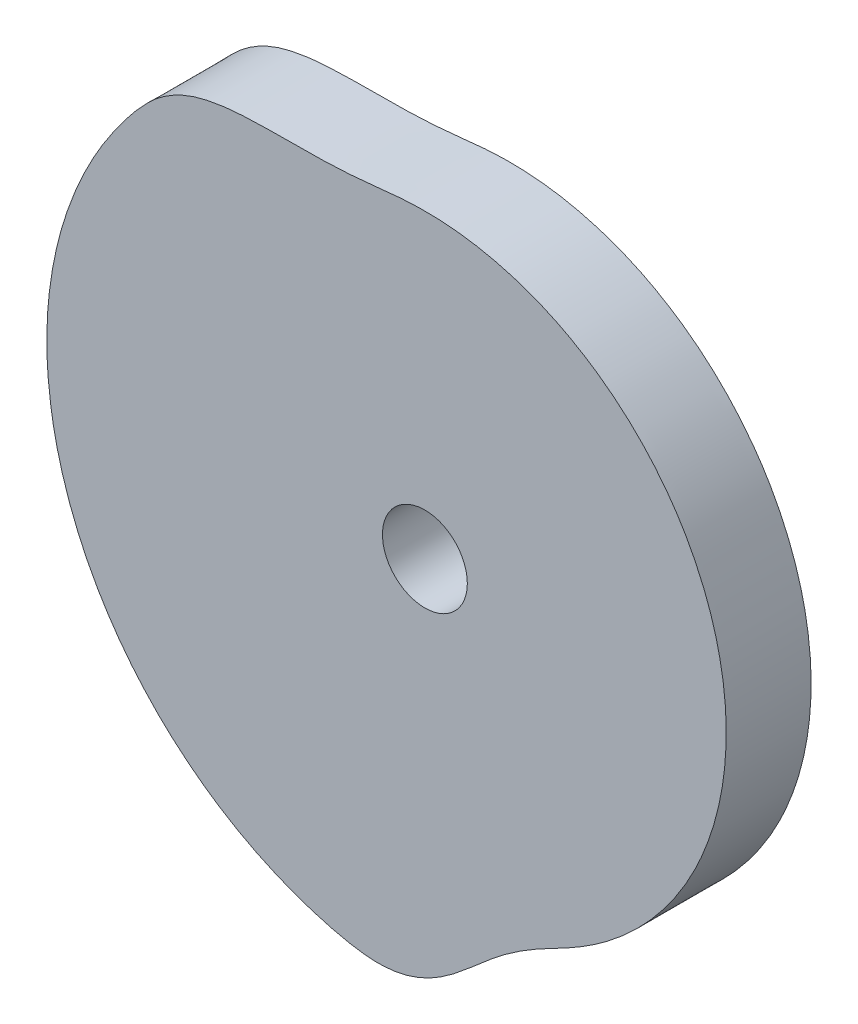
SolidWorks part; units mm, degrees
ref_plane "前视基准面" through (0, 0, 0) normal (0, 0, 1) x (1, 0, 0)
ref_plane "上视基准面" through (0, 0, 0) normal (0, 1, 0) x (1, 0, 0)
ref_plane "右视基准面" through (0, 0, 0) normal (1, 0, 0) x (0, 0, -1)
other "Configuration Table"
curve "曲线1"
sketch "草图1" plane through (0, 0, 0) normal (0, 0, 1) x (1, 0, 0)
  circle A0 centre (0, 0) radius 10
  spline S0 degree 3 poles (-56.239, -69.0587) (-55.6424, -69.5538) (-55.0286, -70.0282) (-54.4224, -70.514) (-53.7986, -70.9782) (-53.1821, -71.454) (-52.5491, -71.9088) (-51.9225, -72.3701) (-51.2913, -72.8232) (-50.6494, -73.2591) (-50.0083, -73.7024) (-49.3669, -74.1387) (-48.7134, -74.5634) (-48.067, -74.9891) (-47.4077, -75.4017) (-46.7483, -75.8126) (-46.0837, -76.2173) (-45.4208, -76.6235) (-44.7476, -77.0117) (-44.0741, -77.3979) (-43.3962, -77.7851) (-42.7137, -78.1573) (-42.0306, -78.5341) (-41.3393, -78.8888) (-40.6521, -79.2508) (-39.9602, -79.6039) (-39.2615, -79.9362) (-38.5659, -80.2853) (-37.8639, -80.6178) (-37.1597, -80.9533) (-36.452, -81.2712) (-35.7394, -81.5786) (-35.03, -81.8944) (-34.3094, -82.1885) (-33.592, -82.4916) (-32.8718, -82.7813) (-32.147, -83.0608) (-31.4222, -83.3424) (-30.6892, -83.6078) (-29.9643, -83.8853) (-29.2245, -84.1271) (-28.4968, -84.3934) (-27.7566, -84.6298) (-27.0218, -84.8723) (-26.2769, -85.1008) (-25.5343, -85.3297) (-24.7887, -85.5537) (-24.0396, -85.7587) (-23.2915, -85.972) (-22.5413, -86.1717) (-21.7868, -86.3604) (-21.0344, -86.5509) (-20.284, -86.7292) (-19.5456, -86.9038) (-18.8127, -87.0471) (-18.0911, -87.202) (-17.3782, -87.3416) (-16.6708, -87.4615) (-15.9739, -87.57) (-15.2847, -87.6737) (-14.6037, -87.7505) (-13.9305, -87.8212) (-13.2674, -87.8834) (-12.6069, -87.9216) (-11.9568, -87.9508) (-11.3102, -87.9735) (-10.6698, -87.975) (-10.0335, -87.9468) (-9.4023, -87.9386) (-8.7796, -87.88) (-8.1595, -87.8216) (-7.5387, -87.7534) (-6.9215, -87.6645) (-6.3092, -87.5508) (-5.7022, -87.4323) (-5.0977, -87.3033) (-4.4945, -87.1513) (-3.8946, -86.9837) (-3.294, -86.8016) (-2.6989, -86.6) (-2.0992, -86.3946) (-1.5063, -86.1623) (-0.9188, -85.9094) (-0.3277, -85.6554) (0.2536, -85.3671) (0.84, -85.0833) (1.4241, -84.7809) (2.0047, -84.4616) (2.5773, -84.121) (3.1547, -83.7811) (3.7252, -83.4213) (4.2885, -83.0378) (4.8647, -82.6649) (5.4226, -82.2556) (5.9917, -81.8535) (6.5521, -81.4295) (7.112, -80.9993) (7.6723, -80.5637) (8.2195, -80.1053) (8.7867, -79.6615) (9.3387, -79.1884) (9.9033, -78.7206) (10.4595, -78.2394) (11.024, -77.7575) (11.5895, -77.2694) (12.1633, -76.7805) (12.7307, -76.277) (13.3106, -75.7767) (13.9041, -75.2815) (14.4867, -74.7655) (15.0946, -74.2721) (15.6872, -73.756) (16.3024, -73.2589) (16.9178, -72.7564) (17.5513, -72.2716) (18.178, -71.7764) (18.8223, -71.2987) (19.4687, -70.817) (20.1274, -70.3497) (20.7911, -69.8915) (21.446, -69.4258) (22.1179, -68.99) (22.791, -68.5615) (23.4562, -68.1252) (24.1363, -67.7226) (24.8106, -67.3211) (25.4745, -66.9172) (26.1512, -66.542) (26.8126, -66.1594) (27.4806, -65.8012) (28.1354, -65.441) (28.7861, -65.0922) (29.4272, -64.748) (30.0663, -64.4256) (30.6897, -64.0894) (31.3058, -63.7617) (31.9152, -63.4405) (32.5162, -63.1355) (33.0993, -62.8186) (33.6763, -62.5155) (34.2329, -62.2025) (34.7829, -61.9017) (35.3191, -61.5885) (35.8611, -61.2841) (36.3895, -60.9592) (36.9199, -60.6398) (37.4525, -60.3208) (37.978, -59.992) (38.5019, -59.6597) (39.0219, -59.3244) (39.5276, -58.9648) (40.0515, -58.6339) (40.5613, -58.2832) (41.0602, -57.9156) (41.5722, -57.5643) (42.0691, -57.1888) (42.5687, -56.8227) (43.0629, -56.4504) (43.5489, -56.0686) (44.0426, -55.6942) (44.5196, -55.2953) (45.0087, -54.9166) (45.483, -54.5162) (45.9585, -54.1222) (46.4326, -53.7234) (46.8894, -53.3055) (47.3625, -52.9032) (47.8194, -52.4829) (48.2691, -52.0555) (48.7331, -51.6471) (49.1688, -51.2053) (49.6201, -50.7835) (50.0623, -50.3489) (50.4992, -49.9125) (50.9329, -49.4694) (51.3594, -49.0194) (51.7897, -48.5729) (52.2124, -48.1188) (52.6294, -47.6625) (53.0429, -47.1992) (53.4492, -46.7293) (53.8606, -46.2633) (54.2586, -45.7889) (54.6637, -45.3226) (55.0483, -44.8386) (55.4437, -44.3623) (55.8192, -43.8694) (56.1998, -43.3798) (56.5804, -42.8929) (56.9515, -42.3978) (57.3239, -41.9019) (57.676, -41.3905) (58.0432, -40.8889) (58.3997, -40.3821) (58.751, -39.8729) (59.0904, -39.3547) (59.4424, -38.8459) (59.7687, -38.3191) (60.1026, -37.7983) (60.4307, -37.2725) (60.7498, -36.7398) (61.0694, -36.2096) (61.3933, -35.6806) (61.7007, -35.1423) (61.9988, -34.5993) (62.3041, -34.0607) (62.5892, -33.5096) (62.8796, -32.9598) (63.1717, -32.4126) (63.4487, -31.8593) (63.7336, -31.3101) (64.0008, -30.7519) (64.2594, -30.1897) (64.5222, -29.6277) (64.779, -29.0644) (65.0317, -28.4974) (65.2804, -27.9316) (65.5249, -27.36) (65.7435, -26.7793) (65.9973, -26.2123) (66.2083, -25.6293) (66.4298, -25.0499) (66.6522, -24.472) (66.8586, -23.8895) (67.0736, -23.3091) (67.2713, -22.7215) (67.4597, -22.1299) (67.6497, -21.5399) (67.8413, -20.9515) (68.0236, -20.3587) (68.1876, -19.7626) (68.3615, -19.1671) (68.5314, -18.5713) (68.692, -17.9714) (68.8388, -17.3697) (68.9923, -16.7714) (69.1313, -16.1669) (69.2666, -15.5626) (69.4181, -14.9598) (69.5225, -14.3511) (69.669, -13.7498) (69.7638, -13.1382) (69.8966, -12.5324) (69.9882, -11.9197) (70.0908, -11.3068) (70.1917, -10.6941) (70.2788, -10.0798) (70.3731, -9.4676) (70.4513, -8.8539) (70.5196, -8.2366) (70.5923, -7.6239) (70.6491, -7.0066) (70.7132, -6.3906) (70.7584, -5.7699) (70.8128, -5.1538) (70.8488, -4.5366) (70.8932, -3.9204) (70.9184, -3.2999) (70.9532, -2.6803) (70.9686, -2.0599) (70.9923, -1.4402) (71.0023, -0.82) (70.9986, -0.2) (71.0033, 0.4201) (70.9884, 1.04) (70.9833, 1.6602) (70.9586, 2.2766) (70.943, 2.8936) (70.9084, 3.5099) (70.8832, 4.1304) (70.8386, 4.7499) (70.8022, 5.3704) (70.7526, 5.9872) (70.689, 6.6032) (70.6296, 7.22) (70.5727, 7.8373) (70.5013, 8.4539) (70.4195, 9.0666) (70.3431, 9.6809) (70.2474, 10.293) (70.1642, 10.9078) (70.0585, 11.5198) (69.9622, 12.1309) (69.8518, 12.741) (69.7295, 13.3499) (69.6108, 13.9568) (69.4911, 14.5643) (69.3604, 15.1668) (69.2303, 15.7741) (69.0936, 16.3783) (68.9386, 16.9796) (68.7926, 17.5815) (68.6297, 18.1799) (68.4683, 18.7795) (68.3175, 19.3807) (68.1247, 19.9674) (67.9648, 20.5668) (67.7674, 21.1548) (67.5925, 21.7518) (67.4025, 22.3386) (67.2005, 22.9247) (66.9878, 23.5047) (66.796, 24.0946) (66.5647, 24.6668) (66.3664, 25.255) (66.1246, 25.8266) (65.9176, 26.4123) (65.6659, 26.9817) (65.4319, 27.5574) (65.1942, 28.13) (64.9359, 28.6915) (64.6949, 29.2604) (64.4282, 29.8192) (64.1723, 30.3827) (63.8983, 30.9392) (63.6345, 31.5005) (63.3484, 32.0492) (63.0719, 32.6027) (62.7792, 33.1496) (62.4919, 33.6977) (62.1998, 34.2469) (61.8932, 34.7833) (61.5879, 35.324) (61.2837, 35.8608) (60.9593, 36.3896) (60.6397, 36.9198) (60.3208, 37.4526) (59.992, 37.978) (59.6597, 38.5019) (59.3244, 39.0219) (58.9648, 39.5276) (58.6339, 40.0515) (58.2832, 40.5613) (57.9156, 41.0602) (57.5643, 41.5722) (57.1888, 42.0691) (56.8227, 42.5687) (56.4504, 43.0629) (56.0686, 43.5489) (55.6942, 44.0426) (55.2953, 44.5196) (54.9166, 45.0087) (54.5162, 45.483) (54.1222, 45.9585) (53.7234, 46.4326) (53.3055, 46.8894) (52.9032, 47.3625) (52.4829, 47.8194) (52.0555, 48.2691) (51.6471, 48.7331) (51.2053, 49.1688) (50.7835, 49.6201) (50.3489, 50.0623) (49.9125, 50.4992) (49.4694, 50.9329) (49.0194, 51.3594) (48.5729, 51.7897) (48.1188, 52.2124) (47.6625, 52.6294) (47.1992, 53.0429) (46.7293, 53.4492) (46.2633, 53.8606) (45.7889, 54.2586) (45.3226, 54.6637) (44.8386, 55.0483) (44.3623, 55.4437) (43.8694, 55.8192) (43.3798, 56.1998) (42.8929, 56.5804) (42.3978, 56.9515) (41.9019, 57.3239) (41.3905, 57.676) (40.8889, 58.0432) (40.3821, 58.3997) (39.8729, 58.751) (39.3547, 59.0904) (38.8459, 59.4424) (38.3191, 59.7687) (37.7983, 60.1026) (37.2725, 60.4307) (36.7398, 60.7498) (36.2096, 61.0694) (35.6806, 61.3933) (35.1423, 61.7007) (34.5993, 61.9988) (34.0607, 62.3041) (33.5096, 62.5892) (32.9598, 62.8796) (32.4126, 63.1717) (31.8593, 63.4487) (31.3101, 63.7336) (30.7519, 64.0008) (30.1897, 64.2594) (29.6277, 64.5222) (29.0644, 64.779) (28.4974, 65.0317) (27.9316, 65.2804) (27.36, 65.5249) (26.7793, 65.7435) (26.2123, 65.9973) (25.6293, 66.2083) (25.0499, 66.4298) (24.472, 66.6522) (23.8895, 66.8586) (23.3091, 67.0736) (22.7215, 67.2713) (22.1299, 67.4597) (21.5399, 67.6496) (20.9516, 67.8416) (20.3614, 68.0215) (19.767, 68.1912) (19.1698, 68.3594) (18.5714, 68.5317) (17.9714, 68.692) (17.3697, 68.8388) (16.7714, 68.9926) (16.1699, 69.1296) (15.5666, 69.2697) (14.9628, 69.4165) (14.3512, 69.5228) (13.7498, 69.6689) (13.1382, 69.7638) (12.5324, 69.8966) (11.9197, 69.9882) (11.3068, 70.0908) (10.6941, 70.1917) (10.0798, 70.2788) (9.4676, 70.3731) (8.8539, 70.4513) (8.2366, 70.5196) (7.6239, 70.5923) (7.0066, 70.6491) (6.3906, 70.7132) (5.7699, 70.7584) (5.1538, 70.8128) (4.5366, 70.8488) (3.9204, 70.8932) (3.2999, 70.9184) (2.6803, 70.9532) (2.0599, 70.9686) (1.4402, 70.9923) (0.82, 71.0023) (0.2, 70.9986) (-0.4201, 71.0033) (-1.04, 70.9884) (-1.6602, 70.9833) (-2.2766, 70.9586) (-2.8936, 70.943) (-3.5099, 70.9084) (-4.1304, 70.8832) (-4.7499, 70.8386) (-5.3704, 70.8024) (-5.9971, 70.7512) (-6.6332, 70.6881) (-7.2873, 70.633) (-7.9492, 70.5549) (-8.628, 70.5065) (-9.3156, 70.4131) (-10.0209, 70.3553) (-10.7357, 70.2642) (-11.4673, 70.2026) (-12.21, 70.1202) (-12.9659, 70.0353) (-13.7307, 69.9743) (-14.5059, 69.886) (-15.2928, 69.817) (-16.0939, 69.7635) (-16.9028, 69.6866) (-17.723, 69.6278) (-18.55, 69.5804) (-19.3867, 69.5299) (-20.2297, 69.4771) (-21.0834, 69.4412) (-21.9397, 69.397) (-22.8034, 69.3705) (-23.6733, 69.3401) (-24.5498, 69.3082) (-25.4332, 69.2868) (-26.3168, 69.2844) (-27.2065, 69.2557) (-28.0967, 69.2522) (-28.9933, 69.2357) (-29.89, 69.2448) (-30.79, 69.2251) (-31.69, 69.235) (-32.59, 69.215) (-33.49, 69.2249) (-34.39, 69.2052) (-35.2867, 69.2142) (-36.1833, 69.1981) (-37.0734, 69.1934) (-37.9633, 69.1691) (-38.8467, 69.1498) (-39.7268, 69.1321) (-40.5969, 69.1026) (-41.4599, 69.0585) (-42.317, 69.0237) (-43.1632, 68.9683) (-44.0009, 68.926) (-44.8265, 68.8481) (-45.644, 68.7839) (-46.4471, 68.7009) (-47.2383, 68.6158) (-48.0133, 68.4996) (-48.7776, 68.3931) (-49.5276, 68.2722) (-50.2644, 68.1426) (-50.9893, 68.0058) (-51.6932, 67.8396) (-52.3899, 67.6865) (-53.0634, 67.5001) (-53.7301, 67.3255) (-54.3757, 67.1238) (-55.0084, 66.9118) (-55.6312, 66.6954) (-56.2338, 66.4513) (-56.832, 66.2159) (-57.4067, 65.9501) (-57.9839, 65.6917) (-58.5505, 65.417) (-59.0965, 65.1097) (-59.6435, 64.8152) (-60.1711, 64.4885) (-60.7035, 64.164) (-61.2205, 63.8122) (-61.7318, 63.4492) (-62.2438, 63.0829) (-62.7455, 62.6901) (-63.2381, 62.2778) (-63.7484, 61.8737) (-64.231, 61.4277) (-64.7255, 60.9793) (-65.2118, 60.5119) (-65.6919, 60.0285) (-66.1791, 59.5355) (-66.6581, 59.0213) (-67.1494, 58.4984) (-67.6176, 57.9479) (-68.1102, 57.3987) (-68.5773, 56.815) (-69.0769, 56.2417) (-69.5518, 55.638) (-70.0291, 55.0293) (-70.5138, 54.4222) (-70.9783, 53.7987) (-71.454, 53.1821) (-71.9088, 52.5491) (-72.3701, 51.9225) (-72.8232, 51.2913) (-73.2591, 50.6494) (-73.7024, 50.0083) (-74.1387, 49.3669) (-74.5634, 48.7134) (-74.9891, 48.067) (-75.4017, 47.4077) (-75.8126, 46.7483) (-76.2173, 46.0837) (-76.6235, 45.4208) (-77.0117, 44.7476) (-77.3979, 44.0741) (-77.7851, 43.3962) (-78.1573, 42.7137) (-78.5341, 42.0306) (-78.8888, 41.3393) (-79.2508, 40.6521) (-79.6039, 39.9602) (-79.9362, 39.2615) (-80.2853, 38.5659) (-80.6178, 37.8639) (-80.9533, 37.1597) (-81.2712, 36.452) (-81.5786, 35.7394) (-81.8944, 35.03) (-82.1885, 34.3094) (-82.4916, 33.592) (-82.7813, 32.8718) (-83.0608, 32.147) (-83.3424, 31.4222) (-83.6078, 30.6892) (-83.8853, 29.9643) (-84.1271, 29.2245) (-84.3934, 28.4968) (-84.6298, 27.7566) (-84.8723, 27.0218) (-85.1008, 26.2769) (-85.3297, 25.5343) (-85.5537, 24.7887) (-85.7587, 24.0396) (-85.9719, 23.2915) (-86.1717, 22.5413) (-86.3604, 21.7868) (-86.5519, 21.0313) (-86.7305, 20.2742) (-86.9004, 19.5168) (-87.0718, 18.7611) (-87.2319, 18.0011) (-87.3803, 17.2367) (-87.5305, 16.4741) (-87.6735, 15.7079) (-87.7973, 14.9429) (-87.9344, 14.1779) (-88.0475, 13.4096) (-88.1757, 12.6418) (-88.2688, 11.8698) (-88.3688, 11.0999) (-88.4762, 10.3282) (-88.5482, 9.5531) (-88.6289, 8.7799) (-88.7161, 8.0078) (-88.7683, 7.2332) (-88.8294, 6.4566) (-88.8953, 5.6841) (-88.9281, 4.9066) (-88.9734, 4.1303) (-88.9983, 3.3533) (-89.0325, 2.5769) (-89.0522, 1.8001) (-89.0588, 1.0233) (-89.0725, 0.2467) (-89.0712, -0.53) (-89.0625, -1.3101) (-89.0387, -2.0866) (-89.023, -2.8635) (-88.9885, -3.6399) (-88.9629, -4.4169) (-88.9208, -5.1936) (-88.873, -5.9671) (-88.8082, -6.7432) (-88.7529, -7.5172) (-88.6815, -8.2938) (-88.5993, -9.0666) (-88.5233, -9.8407) (-88.4277, -10.6097) (-88.3457, -11.3816) (-88.2286, -12.1498) (-88.1199, -12.92) (-88.0119, -13.6908) (-87.8924, -14.4576) (-87.7609, -15.2241) (-87.6203, -15.9867) (-87.4806, -16.7541) (-87.3334, -17.518) (-87.1688, -18.2798) (-87.0118, -19.0411) (-86.8436, -19.7983) (-86.6569, -20.5526) (-86.4846, -21.3086) (-86.2879, -22.0595) (-86.1032, -22.8159) (-85.8923, -23.564) (-85.6778, -24.3127) (-85.4719, -25.0615) (-85.2525, -25.8084) (-85.0219, -26.5517) (-84.7784, -27.2895) (-84.5447, -28.0293) (-84.2864, -28.7621) (-84.0439, -29.4992) (-83.7813, -30.2317) (-83.5088, -30.9595) (-83.2439, -31.6894) (-82.959, -32.4143) (-82.6709, -33.137) (-82.3844, -33.8599) (-82.0762, -34.5717) (-81.784, -35.2898) (-81.471, -36.0019) (-81.1489, -36.7095) (-80.8336, -37.4198) (-80.5009, -38.1221) (-80.1591, -38.8195) (-79.8215, -39.5224) (-79.4715, -40.2175) (-79.1203, -40.9119) (-78.7642, -41.6007) (-78.3852, -42.2807) (-78.0278, -42.9695) (-77.6352, -43.6407) (-77.2641, -44.3209) (-76.8704, -44.9923) (-76.4687, -45.6592) (-76.0743, -46.3313) (-75.6581, -46.9888) (-75.2543, -47.6515) (-74.8286, -48.2991) (-74.4108, -48.9527) (-73.9802, -49.6024) (-73.5416, -50.2477) (-73.1037, -50.8916) (-72.6486, -51.519) (-72.2012, -52.1533) (-71.7386, -52.779) (-71.2835, -53.4118) (-70.8117, -54.028) (-70.34, -54.6426) (-69.8596, -55.2524) (-69.3728, -55.8589) (-68.8795, -56.4596) (-68.3897, -57.0625) (-67.8926, -57.6617) (-67.3819, -58.2484) (-66.87, -58.833) (-66.3493, -59.4094) (-65.833, -59.9894) (-65.3088, -60.562) (-64.7828, -61.1325) (-64.2391, -61.6892) (-63.6991, -62.2524) (-63.1563, -62.8097) (-62.5957, -63.349) (-62.0526, -63.9027) (-61.4919, -64.4422) (-60.9192, -64.9692) (-60.3528, -65.4997) (-59.7792, -66.0228) (-59.1991, -66.539) (-58.6222, -67.0629) (-58.0321, -67.5692) (-57.4386, -68.0723) (-56.843, -68.5703) (-56.239, -69.0587) (-55.6424, -69.5538) (-55.0286, -70.0282) knots -0.004631 -0.003079 -0.00154 0 0.001543 0.003085 0.004632 0.006178 0.007728 0.009278 0.010817 0.012361 0.013904 0.015464 0.016986 0.018551 0.020078 0.021623 0.023184 0.024717 0.026258 0.027816 0.029347 0.030912 0.032451 0.033998 0.035545 0.037082 0.038629 0.040158 0.041722 0.04326 0.044808 0.046348 0.047887 0.049437 0.050988 0.05253 0.054066 0.05562 0.057166 0.058713 0.060247 0.061806 0.063333 0.064879 0.066419 0.067978 0.069512 0.07106 0.072608 0.074151 0.075688 0.077245 0.078778 0.080287 0.081768 0.08323 0.084688 0.086099 0.087508 0.088893 0.090254 0.091593 0.09293 0.094224 0.095537 0.09681 0.098082 0.099354 0.100607 0.101843 0.103081 0.104321 0.105566 0.106798 0.108034 0.109254 0.110483 0.111741 0.112967 0.114224 0.115488 0.116746 0.11802 0.119301 0.120581 0.121888 0.123185 0.124502 0.125838 0.127157 0.128497 0.129858 0.13122 0.132588 0.133983 0.135374 0.136777 0.138193 0.139605 0.141033 0.142486 0.143939 0.145405 0.146871 0.148365 0.149858 0.151365 0.152887 0.154424 0.155974 0.157526 0.159091 0.160659 0.162242 0.163828 0.165414 0.167004 0.16861 0.17022 0.171819 0.173418 0.175011 0.176593 0.178176 0.179754 0.181304 0.182855 0.184386 0.185917 0.187411 0.188905 0.190372 0.191813 0.193244 0.19464 0.196036 0.197405 0.198747 0.200054 0.201361 0.202633 0.203861 0.205098 0.206336 0.207566 0.208796 0.210027 0.211268 0.212492 0.213726 0.214956 0.216191 0.21742 0.218644 0.219885 0.221121 0.222357 0.223578 0.22481 0.226042 0.227272 0.228516 0.22973 0.230972 0.232198 0.233423 0.234663 0.2359 0.237124 0.238362 0.239584 0.240821 0.242044 0.243281 0.244504 0.245741 0.246978 0.248201 0.249439 0.250664 0.251903 0.253143 0.254369 0.255596 0.256825 0.258054 0.259286 0.260519 0.261751 0.262971 0.264208 0.265448 0.266673 0.267913 0.269143 0.270361 0.271607 0.272831 0.274055 0.275296 0.276526 0.277756 0.278987 0.280224 0.281452 0.28268 0.283915 0.285151 0.286387 0.287613 0.28884 0.290076 0.291303 0.29253 0.293775 0.294994 0.296231 0.29746 0.2987 0.299929 0.301162 0.302395 0.303627 0.304853 0.306079 0.307317 0.308549 0.309781 0.311013 0.312239 0.313478 0.314699 0.315938 0.317172 0.318401 0.319631 0.320855 0.322099 0.323323 0.324559 0.325779 0.327011 0.328246 0.329475 0.330703 0.331952 0.333177 0.334402 0.335645 0.336865 0.338105 0.339323 0.340561 0.341798 0.343034 0.344249 0.345483 0.346717 0.347951 0.349184 0.350416 0.351649 0.352881 0.354113 0.355346 0.356578 0.357811 0.359024 0.360257 0.361491 0.362726 0.363961 0.365197 0.366415 0.367653 0.368891 0.370111 0.371353 0.372576 0.373802 0.375047 0.376275 0.377504 0.378736 0.379971 0.381207 0.382423 0.383662 0.384883 0.386126 0.387356 0.388585 0.389819 0.391053 0.392287 0.393513 0.394733 0.395984 0.39721 0.398442 0.399661 0.400906 0.402125 0.403358 0.404584 0.405824 0.407057 0.408286 0.409533 0.410763 0.411981 0.413218 0.414445 0.415672 0.416908 0.418144 0.41937 0.420597 0.421832 0.423068 0.424286 0.425541 0.426752 0.427989 0.429219 0.43045 0.43168 0.432921 0.434145 0.43538 0.436609 0.437844 0.439073 0.440298 0.441538 0.442775 0.444011 0.445231 0.446463 0.447696 0.448925 0.45017 0.451383 0.452625 0.453852 0.455076 0.456316 0.457554 0.458777 0.460015 0.461238 0.462475 0.463698 0.464934 0.466157 0.467394 0.468631 0.469854 0.471092 0.472317 0.473556 0.474796 0.476023 0.477249 0.478478 0.479708 0.48094 0.482172 0.483405 0.484625 0.485861 0.487102 0.488326 0.489567 0.490796 0.492014 0.49326 0.494484 0.495708 0.496949 0.498179 0.49941 0.50064 0.501878 0.503105 0.504333 0.505569 0.506805 0.50804 0.509267 0.510493 0.511729 0.512956 0.514183 0.515428 0.516647 0.517884 0.519113 0.520353 0.521582 0.522815 0.524048 0.525281 0.526507 0.527733 0.528971 0.530203 0.531435 0.532667 0.533892 0.535113 0.536352 0.537592 0.538826 0.540055 0.541284 0.542508 0.543733 0.544977 0.546212 0.547432 0.548664 0.5499 0.551128 0.552357 0.553605 0.55483 0.556056 0.557298 0.558519 0.559759 0.560977 0.562215 0.563451 0.564687 0.565902 0.567137 0.56837 0.569604 0.570837 0.57207 0.573302 0.574534 0.575767 0.576999 0.578231 0.579464 0.580677 0.581911 0.583144 0.584379 0.585614 0.58685 0.588128 0.589425 0.590764 0.592101 0.593481 0.594899 0.596319 0.597777 0.599276 0.600775 0.602311 0.60385 0.605426 0.60702 0.608636 0.61027 0.611923 0.613575 0.615268 0.616959 0.61867 0.62038 0.62211 0.62386 0.625609 0.627378 0.629128 0.630916 0.632685 0.634474 0.636263 0.638052 0.63984 0.641629 0.643418 0.645206 0.646975 0.648764 0.650514 0.652283 0.654032 0.655762 0.657473 0.659184 0.660877 0.662529 0.664184 0.66582 0.667418 0.668998 0.670564 0.67209 0.673599 0.675093 0.67655 0.677997 0.679404 0.680802 0.682162 0.683514 0.684833 0.686141 0.687444 0.68871 0.689973 0.691218 0.69248 0.693725 0.694953 0.696183 0.697424 0.69867 0.699911 0.701163 0.702423 0.703708 0.704993 0.706302 0.707624 0.708974 0.710323 0.711686 0.713106 0.714512 0.715963 0.717414 0.71891 0.720419 0.721946 0.723489 0.725032 0.726578 0.728124 0.729674 0.731225 0.732763 0.734307 0.735851 0.737411 0.738932 0.740497 0.742025 0.743569 0.74513 0.746664 0.748205 0.749763 0.751293 0.752859 0.754397 0.755944 0.757491 0.759029 0.760575 0.762104 0.763668 0.765206 0.766754 0.768294 0.769834 0.771384 0.772934 0.774477 0.776012 0.777566 0.779113 0.78066 0.782193 0.783752 0.785279 0.786825 0.788365 0.789924 0.791459 0.793007 0.794555 0.796097 0.797635 0.799192 0.800744 0.802272 0.80382 0.805364 0.806903 0.808462 0.809998 0.81155 0.813083 0.814631 0.81618 0.817723 0.819266 0.82081 0.822368 0.823906 0.825445 0.827 0.828535 0.83009 0.831622 0.833174 0.834725 0.836257 0.837808 0.839358 0.840888 0.842439 0.843989 0.84554 0.84707 0.848622 0.850173 0.851705 0.853259 0.854794 0.856349 0.857885 0.859443 0.860982 0.862523 0.864063 0.865609 0.867155 0.868701 0.87025 0.871782 0.873338 0.874873 0.876433 0.877976 0.87952 0.881067 0.8826 0.884152 0.88569 0.887228 0.888795 0.890324 0.891871 0.893425 0.894965 0.896511 0.898057 0.899591 0.901143 0.902683 0.90423 0.905777 0.907312 0.908873 0.910416 0.911948 0.913498 0.915038 0.916585 0.918133 0.919671 0.921218 0.922764 0.92432 0.925858 0.927404 0.928943 0.930499 0.93203 0.933578 0.935119 0.936669 0.93822 0.939764 0.941309 0.942847 0.944385 0.945934 0.947494 0.949037 0.950576 0.952114 0.953665 0.955215 0.956761 0.958292 0.959834 0.961389 0.962929 0.964469 0.966021 0.967571 0.969106 0.970654 0.972202 0.973735 0.975282 0.976828 0.978374 0.979934 0.981466 0.983012 0.984558 0.986105 0.987652 0.989185 0.990734 0.992282 0.993832 0.995369 0.996921 0.99846 1 1.001543 1.003085 1.004632 only from (-55.64, -69.55) to (-55.64, -69.55) construction
  spline S1 degree 3 poles (-56.239, -69.0587) (-55.6424, -69.5538) (-55.0286, -70.0282) (-54.4224, -70.514) (-53.7986, -70.9782) (-53.1821, -71.454) (-52.5491, -71.9088) (-51.9225, -72.3701) (-51.2913, -72.8232) (-50.6494, -73.2591) (-50.0083, -73.7024) (-49.3669, -74.1387) (-48.7134, -74.5634) (-48.067, -74.9891) (-47.4077, -75.4017) (-46.7483, -75.8126) (-46.0837, -76.2173) (-45.4208, -76.6235) (-44.7476, -77.0117) (-44.0741, -77.3979) (-43.3962, -77.7851) (-42.7137, -78.1573) (-42.0306, -78.5341) (-41.3393, -78.8888) (-40.6521, -79.2508) (-39.9602, -79.6039) (-39.2615, -79.9362) (-38.5659, -80.2853) (-37.8639, -80.6178) (-37.1597, -80.9533) (-36.452, -81.2712) (-35.7394, -81.5786) (-35.03, -81.8944) (-34.3094, -82.1885) (-33.592, -82.4916) (-32.8718, -82.7813) (-32.147, -83.0608) (-31.4222, -83.3424) (-30.6892, -83.6078) (-29.9643, -83.8853) (-29.2245, -84.1271) (-28.4968, -84.3934) (-27.7566, -84.6298) (-27.0218, -84.8723) (-26.2769, -85.1008) (-25.5343, -85.3297) (-24.7887, -85.5537) (-24.0396, -85.7587) (-23.2915, -85.972) (-22.5413, -86.1717) (-21.7868, -86.3604) (-21.0344, -86.5509) (-20.284, -86.7292) (-19.5456, -86.9038) (-18.8127, -87.0471) (-18.0911, -87.202) (-17.3782, -87.3416) (-16.6708, -87.4615) (-15.9739, -87.57) (-15.2847, -87.6737) (-14.6037, -87.7505) (-13.9305, -87.8212) (-13.2674, -87.8834) (-12.6069, -87.9216) (-11.9568, -87.9508) (-11.3102, -87.9735) (-10.6698, -87.975) (-10.0335, -87.9468) (-9.4023, -87.9386) (-8.7796, -87.88) (-8.1595, -87.8216) (-7.5387, -87.7534) (-6.9215, -87.6645) (-6.3092, -87.5508) (-5.7022, -87.4323) (-5.0977, -87.3033) (-4.4945, -87.1513) (-3.8946, -86.9837) (-3.294, -86.8016) (-2.6989, -86.6) (-2.0992, -86.3946) (-1.5063, -86.1623) (-0.9188, -85.9094) (-0.3277, -85.6554) (0.2536, -85.3671) (0.84, -85.0833) (1.4241, -84.7809) (2.0047, -84.4616) (2.5773, -84.121) (3.1547, -83.7811) (3.7252, -83.4213) (4.2885, -83.0378) (4.8647, -82.6649) (5.4226, -82.2556) (5.9917, -81.8535) (6.5521, -81.4295) (7.112, -80.9993) (7.6723, -80.5637) (8.2195, -80.1053) (8.7867, -79.6615) (9.3387, -79.1884) (9.9033, -78.7206) (10.4595, -78.2394) (11.024, -77.7575) (11.5895, -77.2694) (12.1633, -76.7805) (12.7307, -76.277) (13.3106, -75.7767) (13.9041, -75.2815) (14.4867, -74.7655) (15.0946, -74.2721) (15.6872, -73.756) (16.3024, -73.2589) (16.9178, -72.7564) (17.5513, -72.2716) (18.178, -71.7764) (18.8223, -71.2987) (19.4687, -70.817) (20.1274, -70.3497) (20.7911, -69.8915) (21.446, -69.4258) (22.1179, -68.99) (22.791, -68.5615) (23.4562, -68.1252) (24.1363, -67.7226) (24.8106, -67.3211) (25.4745, -66.9172) (26.1512, -66.542) (26.8126, -66.1594) (27.4806, -65.8012) (28.1354, -65.441) (28.7861, -65.0922) (29.4272, -64.748) (30.0663, -64.4256) (30.6897, -64.0894) (31.3058, -63.7617) (31.9152, -63.4405) (32.5162, -63.1355) (33.0993, -62.8186) (33.6763, -62.5155) (34.2329, -62.2025) (34.7829, -61.9017) (35.3191, -61.5885) (35.8611, -61.2841) (36.3895, -60.9592) (36.9199, -60.6398) (37.4525, -60.3208) (37.978, -59.992) (38.5019, -59.6597) (39.0219, -59.3244) (39.5276, -58.9648) (40.0515, -58.6339) (40.5613, -58.2832) (41.0602, -57.9156) (41.5722, -57.5643) (42.0691, -57.1888) (42.5687, -56.8227) (43.0629, -56.4504) (43.5489, -56.0686) (44.0426, -55.6942) (44.5196, -55.2953) (45.0087, -54.9166) (45.483, -54.5162) (45.9585, -54.1222) (46.4326, -53.7234) (46.8894, -53.3055) (47.3625, -52.9032) (47.8194, -52.4829) (48.2691, -52.0555) (48.7331, -51.6471) (49.1688, -51.2053) (49.6201, -50.7835) (50.0623, -50.3489) (50.4992, -49.9125) (50.9329, -49.4694) (51.3594, -49.0194) (51.7897, -48.5729) (52.2124, -48.1188) (52.6294, -47.6625) (53.0429, -47.1992) (53.4492, -46.7293) (53.8606, -46.2633) (54.2586, -45.7889) (54.6637, -45.3226) (55.0483, -44.8386) (55.4437, -44.3623) (55.8192, -43.8694) (56.1998, -43.3798) (56.5804, -42.8929) (56.9515, -42.3978) (57.3239, -41.9019) (57.676, -41.3905) (58.0432, -40.8889) (58.3997, -40.3821) (58.751, -39.8729) (59.0904, -39.3547) (59.4424, -38.8459) (59.7687, -38.3191) (60.1026, -37.7983) (60.4307, -37.2725) (60.7498, -36.7398) (61.0694, -36.2096) (61.3933, -35.6806) (61.7007, -35.1423) (61.9988, -34.5993) (62.3041, -34.0607) (62.5892, -33.5096) (62.8796, -32.9598) (63.1717, -32.4126) (63.4487, -31.8593) (63.7336, -31.3101) (64.0008, -30.7519) (64.2594, -30.1897) (64.5222, -29.6277) (64.779, -29.0644) (65.0317, -28.4974) (65.2804, -27.9316) (65.5249, -27.36) (65.7435, -26.7793) (65.9973, -26.2123) (66.2083, -25.6293) (66.4298, -25.0499) (66.6522, -24.472) (66.8586, -23.8895) (67.0736, -23.3091) (67.2713, -22.7215) (67.4597, -22.1299) (67.6497, -21.5399) (67.8413, -20.9515) (68.0236, -20.3587) (68.1876, -19.7626) (68.3615, -19.1671) (68.5314, -18.5713) (68.692, -17.9714) (68.8388, -17.3697) (68.9923, -16.7714) (69.1313, -16.1669) (69.2666, -15.5626) (69.4181, -14.9598) (69.5225, -14.3511) (69.669, -13.7498) (69.7638, -13.1382) (69.8966, -12.5324) (69.9882, -11.9197) (70.0908, -11.3068) (70.1917, -10.6941) (70.2788, -10.0798) (70.3731, -9.4676) (70.4513, -8.8539) (70.5196, -8.2366) (70.5923, -7.6239) (70.6491, -7.0066) (70.7132, -6.3906) (70.7584, -5.7699) (70.8128, -5.1538) (70.8488, -4.5366) (70.8932, -3.9204) (70.9184, -3.2999) (70.9532, -2.6803) (70.9686, -2.0599) (70.9923, -1.4402) (71.0023, -0.82) (70.9986, -0.2) (71.0033, 0.4201) (70.9884, 1.04) (70.9833, 1.6602) (70.9586, 2.2766) (70.943, 2.8936) (70.9084, 3.5099) (70.8832, 4.1304) (70.8386, 4.7499) (70.8022, 5.3704) (70.7526, 5.9872) (70.689, 6.6032) (70.6296, 7.22) (70.5727, 7.8373) (70.5013, 8.4539) (70.4195, 9.0666) (70.3431, 9.6809) (70.2474, 10.293) (70.1642, 10.9078) (70.0585, 11.5198) (69.9622, 12.1309) (69.8518, 12.741) (69.7295, 13.3499) (69.6108, 13.9568) (69.4911, 14.5643) (69.3604, 15.1668) (69.2303, 15.7741) (69.0936, 16.3783) (68.9386, 16.9796) (68.7926, 17.5815) (68.6297, 18.1799) (68.4683, 18.7795) (68.3175, 19.3807) (68.1247, 19.9674) (67.9648, 20.5668) (67.7674, 21.1548) (67.5925, 21.7518) (67.4025, 22.3386) (67.2005, 22.9247) (66.9878, 23.5047) (66.796, 24.0946) (66.5647, 24.6668) (66.3664, 25.255) (66.1246, 25.8266) (65.9176, 26.4123) (65.6659, 26.9817) (65.4319, 27.5574) (65.1942, 28.13) (64.9359, 28.6915) (64.6949, 29.2604) (64.4282, 29.8192) (64.1723, 30.3827) (63.8983, 30.9392) (63.6345, 31.5005) (63.3484, 32.0492) (63.0719, 32.6027) (62.7792, 33.1496) (62.4919, 33.6977) (62.1998, 34.2469) (61.8932, 34.7833) (61.5879, 35.324) (61.2837, 35.8608) (60.9593, 36.3896) (60.6397, 36.9198) (60.3208, 37.4526) (59.992, 37.978) (59.6597, 38.5019) (59.3244, 39.0219) (58.9648, 39.5276) (58.6339, 40.0515) (58.2832, 40.5613) (57.9156, 41.0602) (57.5643, 41.5722) (57.1888, 42.0691) (56.8227, 42.5687) (56.4504, 43.0629) (56.0686, 43.5489) (55.6942, 44.0426) (55.2953, 44.5196) (54.9166, 45.0087) (54.5162, 45.483) (54.1222, 45.9585) (53.7234, 46.4326) (53.3055, 46.8894) (52.9032, 47.3625) (52.4829, 47.8194) (52.0555, 48.2691) (51.6471, 48.7331) (51.2053, 49.1688) (50.7835, 49.6201) (50.3489, 50.0623) (49.9125, 50.4992) (49.4694, 50.9329) (49.0194, 51.3594) (48.5729, 51.7897) (48.1188, 52.2124) (47.6625, 52.6294) (47.1992, 53.0429) (46.7293, 53.4492) (46.2633, 53.8606) (45.7889, 54.2586) (45.3226, 54.6637) (44.8386, 55.0483) (44.3623, 55.4437) (43.8694, 55.8192) (43.3798, 56.1998) (42.8929, 56.5804) (42.3978, 56.9515) (41.9019, 57.3239) (41.3905, 57.676) (40.8889, 58.0432) (40.3821, 58.3997) (39.8729, 58.751) (39.3547, 59.0904) (38.8459, 59.4424) (38.3191, 59.7687) (37.7983, 60.1026) (37.2725, 60.4307) (36.7398, 60.7498) (36.2096, 61.0694) (35.6806, 61.3933) (35.1423, 61.7007) (34.5993, 61.9988) (34.0607, 62.3041) (33.5096, 62.5892) (32.9598, 62.8796) (32.4126, 63.1717) (31.8593, 63.4487) (31.3101, 63.7336) (30.7519, 64.0008) (30.1897, 64.2594) (29.6277, 64.5222) (29.0644, 64.779) (28.4974, 65.0317) (27.9316, 65.2804) (27.36, 65.5249) (26.7793, 65.7435) (26.2123, 65.9973) (25.6293, 66.2083) (25.0499, 66.4298) (24.472, 66.6522) (23.8895, 66.8586) (23.3091, 67.0736) (22.7215, 67.2713) (22.1299, 67.4597) (21.5399, 67.6496) (20.9516, 67.8416) (20.3614, 68.0215) (19.767, 68.1912) (19.1698, 68.3594) (18.5714, 68.5317) (17.9714, 68.692) (17.3697, 68.8388) (16.7714, 68.9926) (16.1699, 69.1296) (15.5666, 69.2697) (14.9628, 69.4165) (14.3512, 69.5228) (13.7498, 69.6689) (13.1382, 69.7638) (12.5324, 69.8966) (11.9197, 69.9882) (11.3068, 70.0908) (10.6941, 70.1917) (10.0798, 70.2788) (9.4676, 70.3731) (8.8539, 70.4513) (8.2366, 70.5196) (7.6239, 70.5923) (7.0066, 70.6491) (6.3906, 70.7132) (5.7699, 70.7584) (5.1538, 70.8128) (4.5366, 70.8488) (3.9204, 70.8932) (3.2999, 70.9184) (2.6803, 70.9532) (2.0599, 70.9686) (1.4402, 70.9923) (0.82, 71.0023) (0.2, 70.9986) (-0.4201, 71.0033) (-1.04, 70.9884) (-1.6602, 70.9833) (-2.2766, 70.9586) (-2.8936, 70.943) (-3.5099, 70.9084) (-4.1304, 70.8832) (-4.7499, 70.8386) (-5.3704, 70.8024) (-5.9971, 70.7512) (-6.6332, 70.6881) (-7.2873, 70.633) (-7.9492, 70.5549) (-8.628, 70.5065) (-9.3156, 70.4131) (-10.0209, 70.3553) (-10.7357, 70.2642) (-11.4673, 70.2026) (-12.21, 70.1202) (-12.9659, 70.0353) (-13.7307, 69.9743) (-14.5059, 69.886) (-15.2928, 69.817) (-16.0939, 69.7635) (-16.9028, 69.6866) (-17.723, 69.6278) (-18.55, 69.5804) (-19.3867, 69.5299) (-20.2297, 69.4771) (-21.0834, 69.4412) (-21.9397, 69.397) (-22.8034, 69.3705) (-23.6733, 69.3401) (-24.5498, 69.3082) (-25.4332, 69.2868) (-26.3168, 69.2844) (-27.2065, 69.2557) (-28.0967, 69.2522) (-28.9933, 69.2357) (-29.89, 69.2448) (-30.79, 69.2251) (-31.69, 69.235) (-32.59, 69.215) (-33.49, 69.2249) (-34.39, 69.2052) (-35.2867, 69.2142) (-36.1833, 69.1981) (-37.0734, 69.1934) (-37.9633, 69.1691) (-38.8467, 69.1498) (-39.7268, 69.1321) (-40.5969, 69.1026) (-41.4599, 69.0585) (-42.317, 69.0237) (-43.1632, 68.9683) (-44.0009, 68.926) (-44.8265, 68.8481) (-45.644, 68.7839) (-46.4471, 68.7009) (-47.2383, 68.6158) (-48.0133, 68.4996) (-48.7776, 68.3931) (-49.5276, 68.2722) (-50.2644, 68.1426) (-50.9893, 68.0058) (-51.6932, 67.8396) (-52.3899, 67.6865) (-53.0634, 67.5001) (-53.7301, 67.3255) (-54.3757, 67.1238) (-55.0084, 66.9118) (-55.6312, 66.6954) (-56.2338, 66.4513) (-56.832, 66.2159) (-57.4067, 65.9501) (-57.9839, 65.6917) (-58.5505, 65.417) (-59.0965, 65.1097) (-59.6435, 64.8152) (-60.1711, 64.4885) (-60.7035, 64.164) (-61.2205, 63.8122) (-61.7318, 63.4492) (-62.2438, 63.0829) (-62.7455, 62.6901) (-63.2381, 62.2778) (-63.7484, 61.8737) (-64.231, 61.4277) (-64.7255, 60.9793) (-65.2118, 60.5119) (-65.6919, 60.0285) (-66.1791, 59.5355) (-66.6581, 59.0213) (-67.1494, 58.4984) (-67.6176, 57.9479) (-68.1102, 57.3987) (-68.5773, 56.815) (-69.0769, 56.2417) (-69.5518, 55.638) (-70.0291, 55.0293) (-70.5138, 54.4222) (-70.9783, 53.7987) (-71.454, 53.1821) (-71.9088, 52.5491) (-72.3701, 51.9225) (-72.8232, 51.2913) (-73.2591, 50.6494) (-73.7024, 50.0083) (-74.1387, 49.3669) (-74.5634, 48.7134) (-74.9891, 48.067) (-75.4017, 47.4077) (-75.8126, 46.7483) (-76.2173, 46.0837) (-76.6235, 45.4208) (-77.0117, 44.7476) (-77.3979, 44.0741) (-77.7851, 43.3962) (-78.1573, 42.7137) (-78.5341, 42.0306) (-78.8888, 41.3393) (-79.2508, 40.6521) (-79.6039, 39.9602) (-79.9362, 39.2615) (-80.2853, 38.5659) (-80.6178, 37.8639) (-80.9533, 37.1597) (-81.2712, 36.452) (-81.5786, 35.7394) (-81.8944, 35.03) (-82.1885, 34.3094) (-82.4916, 33.592) (-82.7813, 32.8718) (-83.0608, 32.147) (-83.3424, 31.4222) (-83.6078, 30.6892) (-83.8853, 29.9643) (-84.1271, 29.2245) (-84.3934, 28.4968) (-84.6298, 27.7566) (-84.8723, 27.0218) (-85.1008, 26.2769) (-85.3297, 25.5343) (-85.5537, 24.7887) (-85.7587, 24.0396) (-85.9719, 23.2915) (-86.1717, 22.5413) (-86.3604, 21.7868) (-86.5519, 21.0313) (-86.7305, 20.2742) (-86.9004, 19.5168) (-87.0718, 18.7611) (-87.2319, 18.0011) (-87.3803, 17.2367) (-87.5305, 16.4741) (-87.6735, 15.7079) (-87.7973, 14.9429) (-87.9344, 14.1779) (-88.0475, 13.4096) (-88.1757, 12.6418) (-88.2688, 11.8698) (-88.3688, 11.0999) (-88.4762, 10.3282) (-88.5482, 9.5531) (-88.6289, 8.7799) (-88.7161, 8.0078) (-88.7683, 7.2332) (-88.8294, 6.4566) (-88.8953, 5.6841) (-88.9281, 4.9066) (-88.9734, 4.1303) (-88.9983, 3.3533) (-89.0325, 2.5769) (-89.0522, 1.8001) (-89.0588, 1.0233) (-89.0725, 0.2467) (-89.0712, -0.53) (-89.0625, -1.3101) (-89.0387, -2.0866) (-89.023, -2.8635) (-88.9885, -3.6399) (-88.9629, -4.4169) (-88.9208, -5.1936) (-88.873, -5.9671) (-88.8082, -6.7432) (-88.7529, -7.5172) (-88.6815, -8.2938) (-88.5993, -9.0666) (-88.5233, -9.8407) (-88.4277, -10.6097) (-88.3457, -11.3816) (-88.2286, -12.1498) (-88.1199, -12.92) (-88.0119, -13.6908) (-87.8924, -14.4576) (-87.7609, -15.2241) (-87.6203, -15.9867) (-87.4806, -16.7541) (-87.3334, -17.518) (-87.1688, -18.2798) (-87.0118, -19.0411) (-86.8436, -19.7983) (-86.6569, -20.5526) (-86.4846, -21.3086) (-86.2879, -22.0595) (-86.1032, -22.8159) (-85.8923, -23.564) (-85.6778, -24.3127) (-85.4719, -25.0615) (-85.2525, -25.8084) (-85.0219, -26.5517) (-84.7784, -27.2895) (-84.5447, -28.0293) (-84.2864, -28.7621) (-84.0439, -29.4992) (-83.7813, -30.2317) (-83.5088, -30.9595) (-83.2439, -31.6894) (-82.959, -32.4143) (-82.6709, -33.137) (-82.3844, -33.8599) (-82.0762, -34.5717) (-81.784, -35.2898) (-81.471, -36.0019) (-81.1489, -36.7095) (-80.8336, -37.4198) (-80.5009, -38.1221) (-80.1591, -38.8195) (-79.8215, -39.5224) (-79.4715, -40.2175) (-79.1203, -40.9119) (-78.7642, -41.6007) (-78.3852, -42.2807) (-78.0278, -42.9695) (-77.6352, -43.6407) (-77.2641, -44.3209) (-76.8704, -44.9923) (-76.4687, -45.6592) (-76.0743, -46.3313) (-75.6581, -46.9888) (-75.2543, -47.6515) (-74.8286, -48.2991) (-74.4108, -48.9527) (-73.9802, -49.6024) (-73.5416, -50.2477) (-73.1037, -50.8916) (-72.6486, -51.519) (-72.2012, -52.1533) (-71.7386, -52.779) (-71.2835, -53.4118) (-70.8117, -54.028) (-70.34, -54.6426) (-69.8596, -55.2524) (-69.3728, -55.8589) (-68.8795, -56.4596) (-68.3897, -57.0625) (-67.8926, -57.6617) (-67.3819, -58.2484) (-66.87, -58.833) (-66.3493, -59.4094) (-65.833, -59.9894) (-65.3088, -60.562) (-64.7828, -61.1325) (-64.2391, -61.6892) (-63.6991, -62.2524) (-63.1563, -62.8097) (-62.5957, -63.349) (-62.0526, -63.9027) (-61.4919, -64.4422) (-60.9192, -64.9692) (-60.3528, -65.4997) (-59.7792, -66.0228) (-59.1991, -66.539) (-58.6222, -67.0629) (-58.0321, -67.5692) (-57.4386, -68.0723) (-56.843, -68.5703) (-56.239, -69.0587) (-55.6424, -69.5538) (-55.0286, -70.0282) knots -0.004631 -0.003079 -0.00154 0 0.001543 0.003085 0.004632 0.006178 0.007728 0.009278 0.010817 0.012361 0.013904 0.015464 0.016986 0.018551 0.020078 0.021623 0.023184 0.024717 0.026258 0.027816 0.029347 0.030912 0.032451 0.033998 0.035545 0.037082 0.038629 0.040158 0.041722 0.04326 0.044808 0.046348 0.047887 0.049437 0.050988 0.05253 0.054066 0.05562 0.057166 0.058713 0.060247 0.061806 0.063333 0.064879 0.066419 0.067978 0.069512 0.07106 0.072608 0.074151 0.075688 0.077245 0.078778 0.080287 0.081768 0.08323 0.084688 0.086099 0.087508 0.088893 0.090254 0.091593 0.09293 0.094224 0.095537 0.09681 0.098082 0.099354 0.100607 0.101843 0.103081 0.104321 0.105566 0.106798 0.108034 0.109254 0.110483 0.111741 0.112967 0.114224 0.115488 0.116746 0.11802 0.119301 0.120581 0.121888 0.123185 0.124502 0.125838 0.127157 0.128497 0.129858 0.13122 0.132588 0.133983 0.135374 0.136777 0.138193 0.139605 0.141033 0.142486 0.143939 0.145405 0.146871 0.148365 0.149858 0.151365 0.152887 0.154424 0.155974 0.157526 0.159091 0.160659 0.162242 0.163828 0.165414 0.167004 0.16861 0.17022 0.171819 0.173418 0.175011 0.176593 0.178176 0.179754 0.181304 0.182855 0.184386 0.185917 0.187411 0.188905 0.190372 0.191813 0.193244 0.19464 0.196036 0.197405 0.198747 0.200054 0.201361 0.202633 0.203861 0.205098 0.206336 0.207566 0.208796 0.210027 0.211268 0.212492 0.213726 0.214956 0.216191 0.21742 0.218644 0.219885 0.221121 0.222357 0.223578 0.22481 0.226042 0.227272 0.228516 0.22973 0.230972 0.232198 0.233423 0.234663 0.2359 0.237124 0.238362 0.239584 0.240821 0.242044 0.243281 0.244504 0.245741 0.246978 0.248201 0.249439 0.250664 0.251903 0.253143 0.254369 0.255596 0.256825 0.258054 0.259286 0.260519 0.261751 0.262971 0.264208 0.265448 0.266673 0.267913 0.269143 0.270361 0.271607 0.272831 0.274055 0.275296 0.276526 0.277756 0.278987 0.280224 0.281452 0.28268 0.283915 0.285151 0.286387 0.287613 0.28884 0.290076 0.291303 0.29253 0.293775 0.294994 0.296231 0.29746 0.2987 0.299929 0.301162 0.302395 0.303627 0.304853 0.306079 0.307317 0.308549 0.309781 0.311013 0.312239 0.313478 0.314699 0.315938 0.317172 0.318401 0.319631 0.320855 0.322099 0.323323 0.324559 0.325779 0.327011 0.328246 0.329475 0.330703 0.331952 0.333177 0.334402 0.335645 0.336865 0.338105 0.339323 0.340561 0.341798 0.343034 0.344249 0.345483 0.346717 0.347951 0.349184 0.350416 0.351649 0.352881 0.354113 0.355346 0.356578 0.357811 0.359024 0.360257 0.361491 0.362726 0.363961 0.365197 0.366415 0.367653 0.368891 0.370111 0.371353 0.372576 0.373802 0.375047 0.376275 0.377504 0.378736 0.379971 0.381207 0.382423 0.383662 0.384883 0.386126 0.387356 0.388585 0.389819 0.391053 0.392287 0.393513 0.394733 0.395984 0.39721 0.398442 0.399661 0.400906 0.402125 0.403358 0.404584 0.405824 0.407057 0.408286 0.409533 0.410763 0.411981 0.413218 0.414445 0.415672 0.416908 0.418144 0.41937 0.420597 0.421832 0.423068 0.424286 0.425541 0.426752 0.427989 0.429219 0.43045 0.43168 0.432921 0.434145 0.43538 0.436609 0.437844 0.439073 0.440298 0.441538 0.442775 0.444011 0.445231 0.446463 0.447696 0.448925 0.45017 0.451383 0.452625 0.453852 0.455076 0.456316 0.457554 0.458777 0.460015 0.461238 0.462475 0.463698 0.464934 0.466157 0.467394 0.468631 0.469854 0.471092 0.472317 0.473556 0.474796 0.476023 0.477249 0.478478 0.479708 0.48094 0.482172 0.483405 0.484625 0.485861 0.487102 0.488326 0.489567 0.490796 0.492014 0.49326 0.494484 0.495708 0.496949 0.498179 0.49941 0.50064 0.501878 0.503105 0.504333 0.505569 0.506805 0.50804 0.509267 0.510493 0.511729 0.512956 0.514183 0.515428 0.516647 0.517884 0.519113 0.520353 0.521582 0.522815 0.524048 0.525281 0.526507 0.527733 0.528971 0.530203 0.531435 0.532667 0.533892 0.535113 0.536352 0.537592 0.538826 0.540055 0.541284 0.542508 0.543733 0.544977 0.546212 0.547432 0.548664 0.5499 0.551128 0.552357 0.553605 0.55483 0.556056 0.557298 0.558519 0.559759 0.560977 0.562215 0.563451 0.564687 0.565902 0.567137 0.56837 0.569604 0.570837 0.57207 0.573302 0.574534 0.575767 0.576999 0.578231 0.579464 0.580677 0.581911 0.583144 0.584379 0.585614 0.58685 0.588128 0.589425 0.590764 0.592101 0.593481 0.594899 0.596319 0.597777 0.599276 0.600775 0.602311 0.60385 0.605426 0.60702 0.608636 0.61027 0.611923 0.613575 0.615268 0.616959 0.61867 0.62038 0.62211 0.62386 0.625609 0.627378 0.629128 0.630916 0.632685 0.634474 0.636263 0.638052 0.63984 0.641629 0.643418 0.645206 0.646975 0.648764 0.650514 0.652283 0.654032 0.655762 0.657473 0.659184 0.660877 0.662529 0.664184 0.66582 0.667418 0.668998 0.670564 0.67209 0.673599 0.675093 0.67655 0.677997 0.679404 0.680802 0.682162 0.683514 0.684833 0.686141 0.687444 0.68871 0.689973 0.691218 0.69248 0.693725 0.694953 0.696183 0.697424 0.69867 0.699911 0.701163 0.702423 0.703708 0.704993 0.706302 0.707624 0.708974 0.710323 0.711686 0.713106 0.714512 0.715963 0.717414 0.71891 0.720419 0.721946 0.723489 0.725032 0.726578 0.728124 0.729674 0.731225 0.732763 0.734307 0.735851 0.737411 0.738932 0.740497 0.742025 0.743569 0.74513 0.746664 0.748205 0.749763 0.751293 0.752859 0.754397 0.755944 0.757491 0.759029 0.760575 0.762104 0.763668 0.765206 0.766754 0.768294 0.769834 0.771384 0.772934 0.774477 0.776012 0.777566 0.779113 0.78066 0.782193 0.783752 0.785279 0.786825 0.788365 0.789924 0.791459 0.793007 0.794555 0.796097 0.797635 0.799192 0.800744 0.802272 0.80382 0.805364 0.806903 0.808462 0.809998 0.81155 0.813083 0.814631 0.81618 0.817723 0.819266 0.82081 0.822368 0.823906 0.825445 0.827 0.828535 0.83009 0.831622 0.833174 0.834725 0.836257 0.837808 0.839358 0.840888 0.842439 0.843989 0.84554 0.84707 0.848622 0.850173 0.851705 0.853259 0.854794 0.856349 0.857885 0.859443 0.860982 0.862523 0.864063 0.865609 0.867155 0.868701 0.87025 0.871782 0.873338 0.874873 0.876433 0.877976 0.87952 0.881067 0.8826 0.884152 0.88569 0.887228 0.888795 0.890324 0.891871 0.893425 0.894965 0.896511 0.898057 0.899591 0.901143 0.902683 0.90423 0.905777 0.907312 0.908873 0.910416 0.911948 0.913498 0.915038 0.916585 0.918133 0.919671 0.921218 0.922764 0.92432 0.925858 0.927404 0.928943 0.930499 0.93203 0.933578 0.935119 0.936669 0.93822 0.939764 0.941309 0.942847 0.944385 0.945934 0.947494 0.949037 0.950576 0.952114 0.953665 0.955215 0.956761 0.958292 0.959834 0.961389 0.962929 0.964469 0.966021 0.967571 0.969106 0.970654 0.972202 0.973735 0.975282 0.976828 0.978374 0.979934 0.981466 0.983012 0.984558 0.986105 0.987652 0.989185 0.990734 0.992282 0.993832 0.995369 0.996921 0.99846 1 1.001543 1.003085 1.004632 only from (-55.64, -69.55) to (-55.64, -69.55)
extrude "凸台-拉伸1" add sketch "草图1" along normal blind 20
